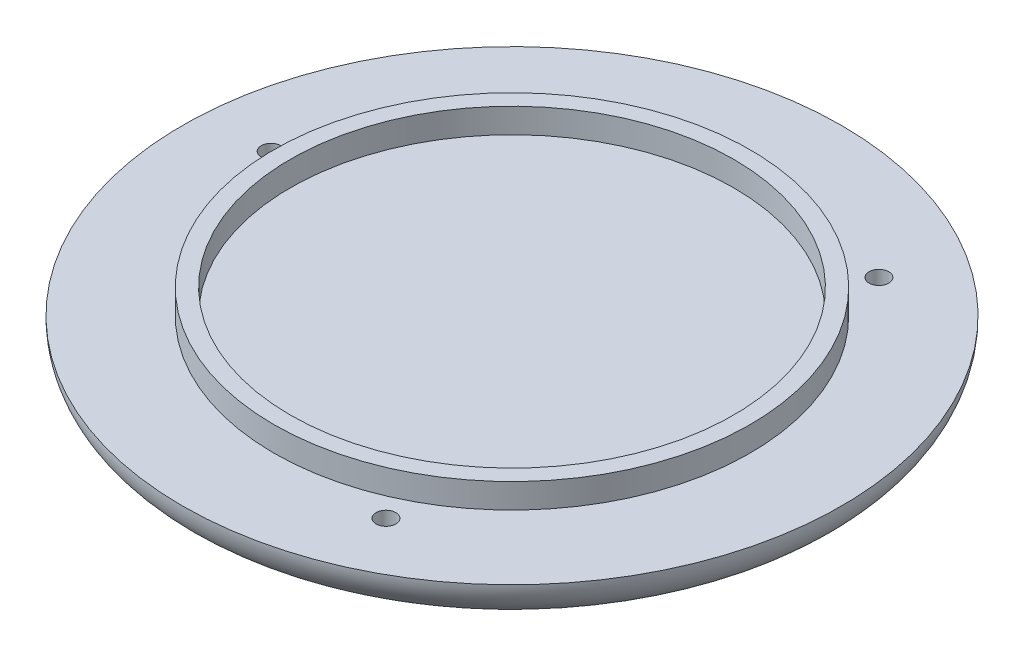
SolidWorks part; units mm, degrees
ref_plane "前视基准面" through (0, 0, 0) normal (0, 0, 1) x (1, 0, 0)
ref_plane "上视基准面" through (0, 0, 0) normal (0, 1, 0) x (1, 0, 0)
ref_plane "右视基准面" through (0, 0, 0) normal (1, 0, 0) x (0, 0, -1)
sketch "草图1" plane through (0, 0, 0) normal (0, 1, 0) x (1, 0, 0)
  circle A0 centre (0, 0) radius 40
  dimension "D1" = 80
extrude "凸台-拉伸1" add sketch "草图1" along normal blind 5
sketch "草图2" plane through (0, 5, 0) normal (0, 1, 0) x (1, 0, 0)
  circle A0 centre (0, 0) radius 28.9
  dimension "D1" = 57.8
extrude "凸台-拉伸2" add sketch "草图2" along normal blind 3
sketch "草图4" plane through (0, 0, 0) normal (0, -1, 0) x (1, 0, 0)
  circle A1 centre (0, 0) radius 32
  circle A2 centre (0, 0) radius 32 construction
hole_wizard "打孔尺寸(%根据)内六角圆柱头螺钉的类型1" positions "草图5" profile "草图6" counterbore size "M2" standard "GB" end condition up to next
sketch "草图5" plane through (0, 0, 0) normal (0, -1, 0) x (-1, 0, 0)
  circle A0 centre (0, 0) radius 32 construction
  point P0 (-13.645, -28.945)
sketch "草图6" plane through (13.645, 0, 28.945) normal (1, 0, 0) x (0, 0, -1)
  line L0 (0, 0) -> (0, 5)
  line L1 (0, 5) -> (1.2, 5)
  line L3 (1.2, 5) -> (1.2, 2.3)
  line L4 (1.2, 2.3) -> (2.15, 2.3)
  line L5 (2.15, 2.3) -> (2.15, 0)
  line L7 (2.15, 0) -> (0, 0)
  line L11 (0, -6.35) -> (0, 107.95) construction
  dimension "通孔孔直径" = 2.4
  dimension "通孔孔深度" = 5
  dimension "柱形沉头孔直径" = 4.3
  dimension "柱形沉头孔深度" = 2.3
pattern_circular "阵列(圆周)1" count 3 over 360 about axis through (0, 5, 0) along (0, -1, 0) of "打孔尺寸(%根据)内六角圆柱头螺钉的类型1"
sketch "草图7" plane through (0, 8, 0) normal (0, 1, 0) x (1, 0, 0)
  circle A0 centre (0, 0) radius 26.9
  circle A1 centre (0, 0) radius 28.9 construction
  dimension "D1" = 2
extrude "切除-拉伸1" cut sketch "草图7" against normal up to surface (3 mm away) up to face at (18.2446, 5, -25.0894)
fillet "圆角1" radius 5 1 edges at (0, 0, 40)
